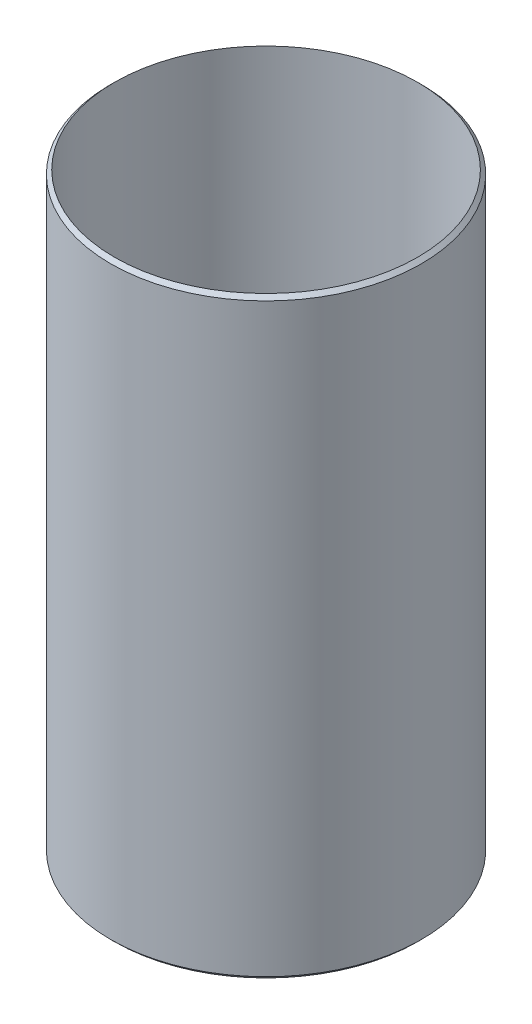
SolidWorks part; units mm, degrees
material "6061-T6 (SS)"
ref_plane "Front Plane" through (0, 0, 0) normal (0, 0, 1) x (1, 0, 0)
ref_plane "Top Plane" through (0, 0, 0) normal (0, 1, 0) x (1, 0, 0)
ref_plane "Right Plane" through (0, 0, 0) normal (1, 0, 0) x (0, 0, -1)
sketch "Sketch1" plane through (0, 0, 0) normal (0, 1, 0) x (1, 0, 0)
  circle A0 centre (0, 0) radius 80.55
  circle A1 centre (0, 0) radius 82.55
  dimension "D1" = 165.1
  dimension "D2" = 2
extrude "Boss-Extrude1" add sketch "Sketch1" along normal blind 315
chamfer "Chamfer1" distance 2 angle 45 2 edges at (0, 0, 82.55) (0, 315, 82.55)
equation "\"TubeDiameter\"= 6.500in"
equation "\"D1@Sketch1\"=\"TubeDiameter\""
